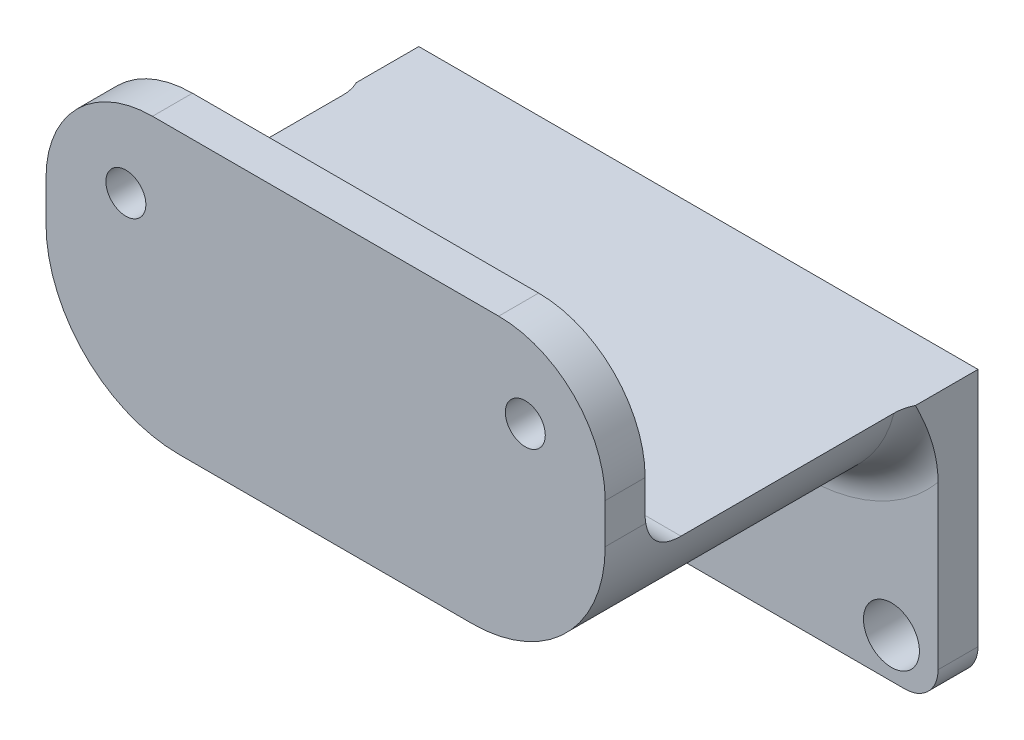
SolidWorks part; units mm, degrees
ref_plane "Front Plane" through (0, 0, 0) normal (0, 0, 1) x (1, 0, 0)
ref_plane "Top Plane" through (0, 0, 0) normal (0, 1, 0) x (1, 0, 0)
ref_plane "Right Plane" through (0, 0, 0) normal (1, 0, 0) x (0, 0, -1)
sketch "Sketch3" plane through (0, 0, 0) normal (0, 0, 1) x (1, 0, 0)
  line L0 (-22.5928, 14.5094) -> (-6.0928, 14.5094)
  line L1 (-48.0928, 14.5094) -> (-31.5928, 14.5094)
  line L2 (-48.0928, 14.5094) -> (-48.0928, 3.5094)
  line L3 (-38.0928, -6.4906) -> (-16.0928, -6.4906)
  line L4 (-6.0928, 14.5094) -> (-6.0928, 3.5094)
  line L5 (-31.5928, 14.5094) -> (-22.5928, 14.5094)
  circle A1 centre (-42.0928, 8.5094) radius 1.5
  circle A2 centre (-12.0928, 8.5094) radius 1.5
  arc A3 (-48.0928, 3.5094) -> (-38.0928, -6.4906) centre (-38.0928, 3.5094) ccw
  arc A4 (-16.0928, -6.4906) -> (-6.0928, 3.5094) centre (-16.0928, 3.5094) ccw
  point P4 (0, 0)
  point P12 (-27.0928, -6.4906)
  point P16 (-48.0928, -6.4906)
  dimension "D4" = 3
  dimension "D5" = 3
  dimension "D12" = 10
  dimension "D13" = 10
  dimension "42" = 42
  dimension "D2" = 21
  dimension "D6" = 15
  dimension "D9" = 15
  dimension "D10" = 15
extrude "Boss-Extrude3" add sketch "Sketch3" along normal blind 3
sketch "Sketch6" plane through (0, 0, 0) normal (0, 0, 1) x (1, 0, 0)
  line L7 (-6.4012, 1.0453) -> (-47.7845, 1.0453)
  line L8 (-38.0928, -6.4906) -> (-16.0928, -6.4906) construction
  line L9 (-38.0928, -6.4906) -> (-16.0928, -6.4906)
  arc A5 (-16.0928, -6.4906) -> (-6.0928, 3.5094) centre (-16.0928, 3.5094) ccw construction
  arc A6 (-16.0928, -6.4906) -> (-6.4012, 1.0453) centre (-16.0928, 3.5094) ccw
  arc A7 (-48.0928, 3.5094) -> (-38.0928, -6.4906) centre (-38.0928, 3.5094) ccw construction
  arc A8 (-47.7845, 1.0453) -> (-38.0928, -6.4906) centre (-38.0928, 3.5094) ccw
extrude "Boss-Extrude4" add sketch "Sketch6" against normal blind 25
ref_plane "Plane7" through (0, 1.0453, 0) normal (0, 1, 0) x (1, 0, 0)
sketch "Sketch9" plane through (0, 1.0453, 0) normal (0, 1, 0) x (1, 0, 0)
  line L1 (-6.0928, 25) -> (-48.0928, 25)
  line L2 (-6.0928, 25) -> (-6.0928, 22)
  line L3 (-6.0928, 22) -> (-48.0928, 22)
  line L4 (-48.0928, 25) -> (-48.0928, 22)
  dimension "D1" = 42
  dimension "D2" = 3
fillet "Fillet4" radius 8 2 edges at (-48.0928, 14.5094, 1.5) (-6.0928, 14.5094, 1.5)
extrude "Boss-Extrude7" add sketch "Sketch9" against normal blind 30
fillet "Fillet6" radius 5 1 edges at (-6.0928, -28.9547, -23.5)
fillet "Fillet7" radius 5 1 edges at (-48.0928, -28.9547, -23.5)
ref_plane "Plane13" through (0, 0, -25) normal (0, 0, -1) x (-1, 0, 0)
sketch "Sketch11" plane through (0, 0, -25) normal (0, 0, -1) x (-1, 0, 0)
  line L0 (6.0928, -19.4906) -> (6.0928, 5.5094) construction
  line L3 (22.5928, -24.4906) -> (31.5928, -24.4906)
  line L4 (48.0928, 5.5094) -> (48.0928, -19.4906) construction
  arc A0 (31.5928, -24.4906) -> (22.5928, -24.4906) centre (27.0928, -24.4906) ccw
  circle A1 centre (9.5928, -16.4906) radius 2.1
  circle A2 centre (44.5928, -16.4906) radius 2.1
  dimension "D4" = 8
  dimension "D1" = 4.2
  dimension "D2" = 35
  dimension "D3" = 17.5
  dimension "D5" = 8
  dimension "D6" = 17.5
  dimension "D7" = 21
  dimension "D8" = 21
  dimension "D9" = 3.5
  dimension "D10" = 3.5
extrude "Cut-Extrude2" cut sketch "Sketch11" against normal blind 30
sketch "Sketch12" plane through (0, 0, -25) normal (0, 0, -1) x (-1, 0, 0)
  line L2 (6.0928, -19.4906) -> (50.3785, -19.4906)
  line L3 (6.0928, -19.4906) -> (6.0928, -37.95)
  line L4 (6.0928, -37.95) -> (50.3785, -37.95)
  line L5 (50.3785, -19.4906) -> (50.3785, -37.95)
extrude "Cut-Extrude3" cut sketch "Sketch12" against normal blind 10
fillet "Fillet8" radius 2.5 2 edges at (-48.0928, -19.4906, -23.5) (-6.0928, -19.4906, -23.5)
fillet "Fillet9" radius 3 1 edges at (-27.0928, 1.0453, 0)
fillet "Fillet10" radius 3 3 edges at (-44.2312, -4.385, -22) (-9.9544, -4.385, -22) (-27.0928, -6.4906, -22)
